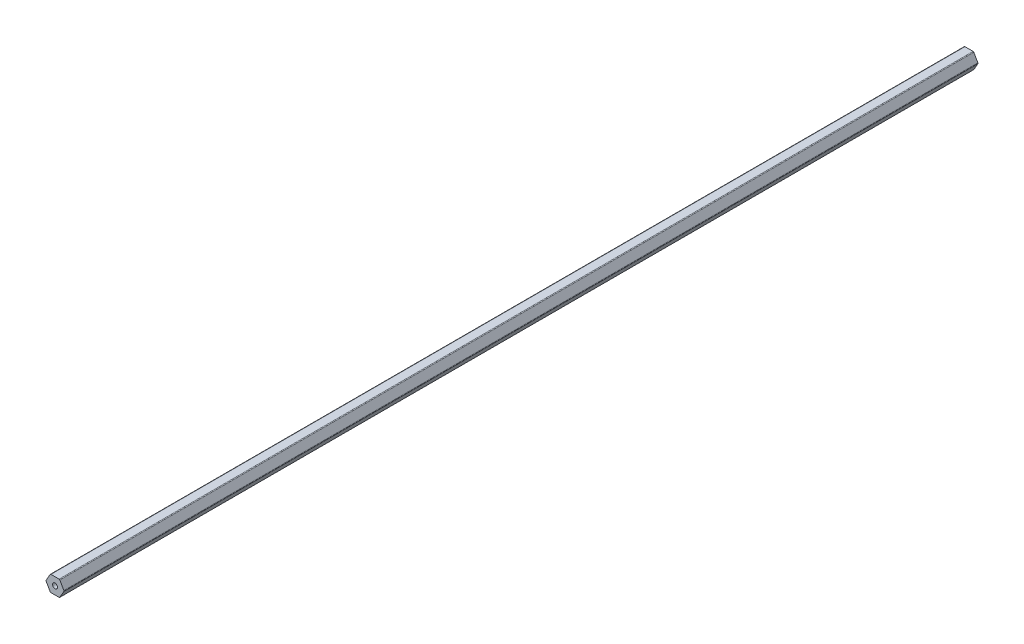
SolidWorks part; units mm, degrees
material "7075-T6 (SN)"
ref_plane "Front Plane" through (0, 0, 0) normal (0, 0, 1) x (1, 0, 0)
ref_plane "Top Plane" through (0, 0, 0) normal (0, 1, 0) x (1, 0, 0)
ref_plane "Right Plane" through (0, 0, 0) normal (1, 0, 0) x (0, 0, -1)
other "Configuration Table"
sketch "Sketch1" plane through (0, 0, 0) normal (0, 0, 1) x (1, 0, 0)
  line L1 (6.35, 0) -> (3.175, 5.4993)
  line L2 (3.175, 5.4993) -> (-3.175, 5.4993)
  line L3 (-3.175, 5.4993) -> (-6.35, 0)
  line L4 (-6.35, 0) -> (-3.175, -5.4993)
  line L5 (-3.175, -5.4993) -> (3.175, -5.4993)
  line L6 (3.175, -5.4993) -> (6.35, 0)
  circle A0 centre (0, 0) radius 5.4993 construction
  circle A1 centre (0, 0) radius 1.7145
  dimension "D2" = 3.429
  dimension "D1" = 12.7
extrude "Boss-Extrude1" add sketch "Sketch1" along normal mid plane 635
fillet "Fillet1" radius 0.635 6 edges at (3.175, -5.4993, 0) (-3.175, -5.4993, 0) (-6.35, 0, 0) (-3.175, 5.4993, 0) (3.175, 5.4993, 0) (6.35, 0, 0)
equation "\"length\"= 25"
equation "\"D1@Boss-Extrude1\"=\"length\""
